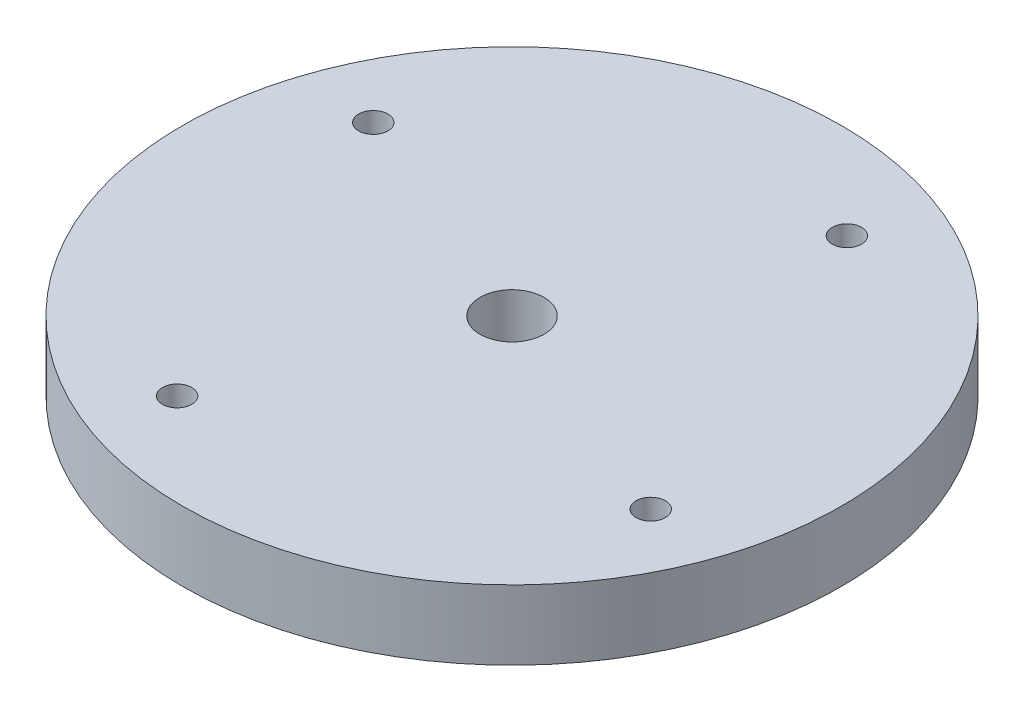
SolidWorks part; units mm, degrees
material "Balsa"
ref_plane "Front Plane" through (0, 0, 0) normal (0, 0, 1) x (1, 0, 0)
ref_plane "Top Plane" through (0, 0, 0) normal (0, 1, 0) x (1, 0, 0)
ref_plane "Right Plane" through (0, 0, 0) normal (1, 0, 0) x (0, 0, -1)
sketch "Sketch1" plane through (0, 0, 0) normal (0, 1, 0) x (1, 0, 0)
  circle A0 centre (0, 0) radius 90
  dimension "D1" = 180
extrude "Boss-Extrude1" add sketch "Sketch1" along normal blind 9.5 and the other way blind 9.5
hole_wizard "CSK for M8 SFHCS2" positions "Sketch6" profile "Sketch7" countersink size "M8" standard "ANSI Metric" end condition through all
sketch "Sketch6" plane through (0, -9.5, 0) normal (0, -1, 0) x (-1, 0, 0)
  point P0 (0, 0)
sketch "Sketch7" plane through (0, -9.5, 0) normal (1, 0, 0) x (0, 0, -1)
  line L0 (0, 0) -> (0, 19)
  line L1 (0, 19) -> (8.75, 19)
  line L2 (8.75, 19) -> (8.75, 0.21)
  line L3 (8.75, 0.21) -> (8.96, 0)
  line L5 (8.96, 0) -> (0, 0)
  line L6 (-8.75, 0.21) -> (-8.96, 0) construction
  line L11 (0, -6.35) -> (0, 107.95) construction
  dimension "Thru Hole Dia." = 17.5
  dimension "Thru Hole Depth" = 19
  dimension "Near C'Sink Dia." = 17.92
  dimension "Near C'Sink Angle" = 90
sketch "Sketch8" plane through (0, 0, 0) normal (0, 1, 0) x (1, 0, 0)
  line L0 (0, 0) -> (26.7878, 64.6716) construction
  line L1 (0, 0) -> (90, 0) construction
  circle A0 centre (0, 0) radius 90 construction
  circle A1 centre (26.7878, 64.6716) radius 4
  point P11 (0, 0)
  dimension "D3" = 8
  dimension "D1" = 67.5
  dimension "D2" = 70
extrude "Cut-Extrude3" cut sketch "Sketch8" against normal through all both and the other way through all
pattern_circular "CirPattern2" count 4 over 360 about axis through (0, 9.5, 0) along (0, -1, 0) of "Cut-Extrude3"
